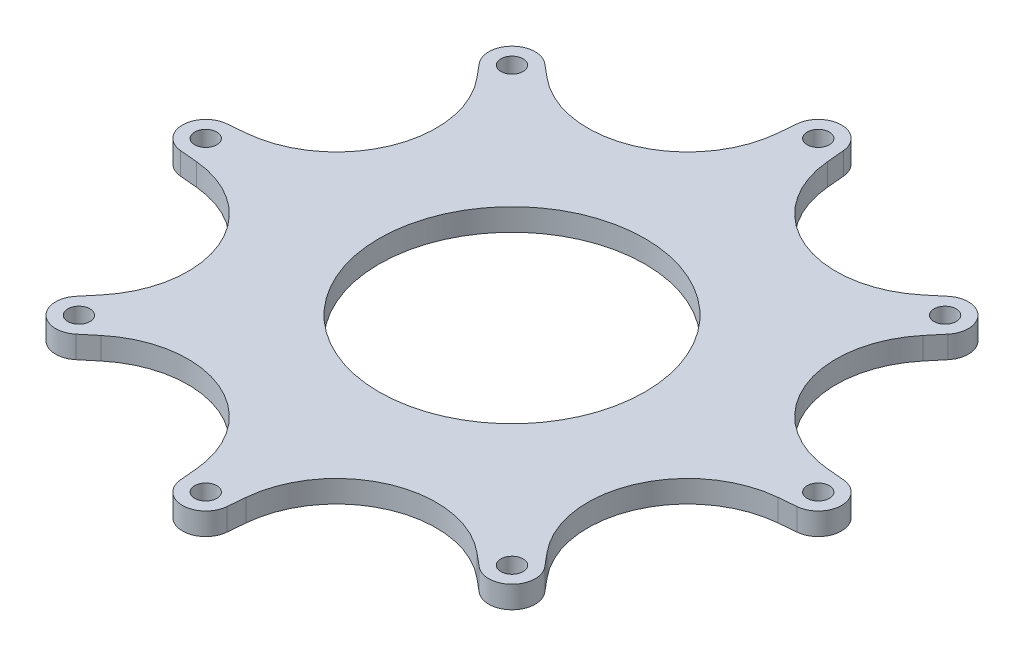
SolidWorks part; units mm, degrees
material "Thornel Mat VMA"
ref_plane "Front Plane" through (0, 0, 0) normal (0, 0, 1) x (1, 0, 0)
ref_plane "Top Plane" through (0, 0, 0) normal (0, 1, 0) x (1, 0, 0)
ref_plane "Right Plane" through (0, 0, 0) normal (1, 0, 0) x (0, 0, -1)
sketch "Sketch1" plane through (0, 0, 0) normal (0, 1, 0) x (1, 0, 0)
  line L0 (0, 0) -> (73.1675, 0) construction
  line L1 (0, 0) -> (67.598, 28) construction
  line L2 (0, 0) -> (67.598, -28) construction
  line L3 (67.598, 28) -> (67.598, -28) construction
  line L4 (69.5723, 5.2285) -> (65.5653, 5.592)
  line L5 (69.5723, -5.2285) -> (65.5653, -5.592)
  line L6 (52.8921, -45.4979) -> (50.3158, -42.4076)
  line L7 (45.4979, -52.8921) -> (42.4076, -50.3158)
  line L8 (5.2285, -69.5723) -> (5.592, -65.5653)
  line L9 (-5.2285, -69.5723) -> (-5.592, -65.5653)
  line L10 (-45.4979, -52.8921) -> (-42.4076, -50.3158)
  line L11 (-52.8921, -45.4979) -> (-50.3158, -42.4076)
  line L12 (-69.5723, -5.2285) -> (-65.5653, -5.592)
  line L13 (-69.5723, 5.2285) -> (-65.5653, 5.592)
  line L14 (-52.8921, 45.4979) -> (-50.3158, 42.4076)
  line L15 (-45.4979, 52.8921) -> (-42.4076, 50.3158)
  line L16 (-5.2285, 69.5723) -> (-5.592, 65.5653)
  line L17 (5.2285, 69.5723) -> (5.592, 65.5653)
  line L18 (45.4979, 52.8921) -> (42.4076, 50.3158)
  line L19 (52.8921, 45.4979) -> (50.3158, 42.4076)
  circle A0 centre (0, 0) radius 73.1675 construction
  circle A1 centre (67.598, 28) radius 22.5
  circle A3 centre (69.098, 0) radius 5.25
  circle A4 centre (67.598, -28) radius 22.5
  circle A5 centre (48.8597, -48.8597) radius 5.25
  circle A6 centre (28, -67.598) radius 22.5
  circle A7 centre (0, -69.098) radius 5.25
  circle A8 centre (-28, -67.598) radius 22.5
  circle A9 centre (-48.8597, -48.8597) radius 5.25
  circle A10 centre (-67.598, -28) radius 22.5
  circle A11 centre (-69.098, 0) radius 5.25
  circle A12 centre (-67.598, 28) radius 22.5
  circle A13 centre (-48.8597, 48.8597) radius 5.25
  circle A14 centre (-28, 67.598) radius 22.5
  circle A15 centre (0, 69.098) radius 5.25
  circle A16 centre (28, 67.598) radius 22.5
  circle A17 centre (48.8597, 48.8597) radius 5.25
  point P71 (0, 0)
  dimension "D1" = 45
  dimension "D5" = 10.5
  dimension "D2" = 22.5
  dimension "D3" = 22.5
  dimension "D4" = 56
  dimension "D6" = 1.5
  dimension "D7" = 8
extrude "Boss-Extrude1" add sketch "Sketch1" along normal blind 5 contours A17 L18 A16 L17 A15 L16 A14 L15 A13 L14 A12 L13 A11 L12 A10 L11 A9 L10 A8 L9 A7 L8 A6 L7 A5 L6 A4 L5 A3 L4 A1 L19 | A7 | A5 | A3 | A17 | A9 | A11 | A13 | A15 region at (0, 0, 0) region at (69.098, 0, 0) region at (48.8597, 0, -48.8597) region at (48.8597, 0, 48.8597) region at (0, 0, -69.098) region at (0, 0, 69.098) region at (-48.8597, 0, -48.8597) region at (-48.8597, 0, 48.8597) region at (-69.098, 0, 0)
sketch "Sketch2" plane through (0, 5, 0) normal (0, 1, 0) x (1, 0, 0)
  circle A0 centre (0, 0) radius 69.098 construction
  circle A1 centre (69.098, 0) radius 2.5
  circle A2 centre (48.8597, -48.8597) radius 2.5
  circle A3 centre (0, -69.098) radius 2.5
  circle A4 centre (-48.8597, -48.8597) radius 2.5
  circle A5 centre (-69.098, 0) radius 2.5
  circle A6 centre (-48.8597, 48.8597) radius 2.5
  circle A7 centre (0, 69.098) radius 2.5
  circle A8 centre (48.8597, 48.8597) radius 2.5
  point P22 (0, 0)
  dimension "D1" = 5
  dimension "D2" = 8
extrude "Cut-Extrude1" cut sketch "Sketch2" against normal blind 10
sketch "Sketch3" plane through (0, 5, 0) normal (0, 1, 0) x (1, 0, 0)
  circle A0 centre (0, 0) radius 30
  dimension "D1" = 60
extrude "Cut-Extrude2" cut sketch "Sketch3" against normal blind 10
